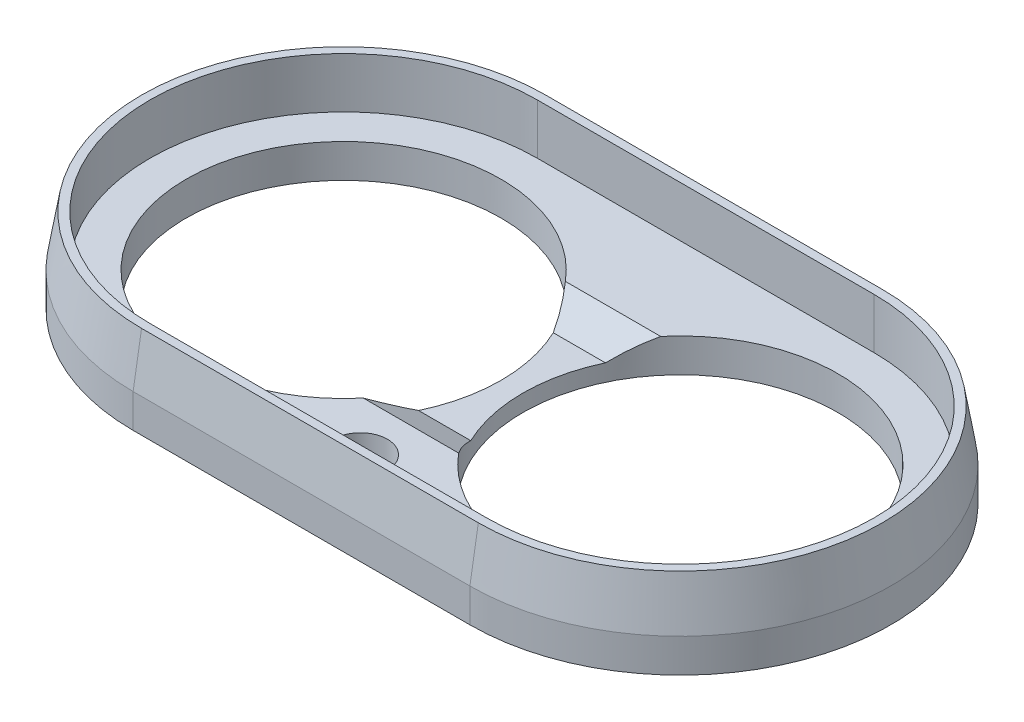
SolidWorks part; units mm, degrees
ref_plane "Front Plane" through (0, 0, 0) normal (0, 0, 1) x (1, 0, 0)
ref_plane "Top Plane" through (0, 0, 0) normal (0, 1, 0) x (1, 0, 0)
ref_plane "Right Plane" through (0, 0, 0) normal (1, 0, 0) x (0, 0, -1)
sketch "Sketch1" plane through (0, 0, 0) normal (0, 1, 0) x (1, 0, 0)
  line L0 (-10, 0) -> (10, 0)
  line L1 (10, 0) -> (22.5, 0)
  line L2 (10, 12.5) -> (-10, 12.5)
  line L3 (0, 12.5) -> (0, -12.5)
  line L4 (0, 19.9863) -> (0, -22.3991) construction
  line L5 (33.4627, 0) -> (-36.5916, 0) construction
  line L6 (-10, 0) -> (-22.5, 0)
  line L7 (10, -12.5) -> (-10, -12.5)
  arc A0 (10, -12.5) -> (10, 12.5) centre (10, 0) ccw
  arc A1 (-10, -12.5) -> (-10, 12.5) centre (-10, 0) cw
  point P16 (0, 0)
  dimension "D1" = 10
extrude "Boss-Extrude1" add sketch "Sketch1" along normal blind 2 contours A1 L6 L0 L3 L2 | A1 L7 L3 L0 L6 | L7 A0 L1 L0 L3 | L1 A0 L2 L3 L0 region at (-10.1051, 0, -5.7819) region at (-10.1051, 0, 5.7819) region at (10.1051, 0, -5.7819) region at (10.1051, 0, 5.7819)
sketch "Sketch2" plane through (0, 2, 0) normal (0, 1, 0) x (1, 0, 0)
  line L0 (0, 15.683) -> (0, -16.5594) construction
  circle A1 centre (10, 0) radius 9.35
  circle A2 centre (-10, 0) radius 9.35
  dimension "D1" = 18.7
  dimension "D2" = 10
extrude "Cut-Extrude1" cut sketch "Sketch2" against normal through all
sketch "Sketch3" plane through (0, 2, 0) normal (0, 1, 0) x (1, 0, 0)
  line L2 (10, 11.5) -> (-10, 11.5)
  line L3 (-10, -11.5) -> (10, -11.5)
  line L4 (-10, -12.5) -> (10, -12.5)
  line L5 (10, 12.5) -> (-10, 12.5)
  line L6 (-10, -12.5) -> (10, -12.5)
  line L7 (10, 12.5) -> (-10, 12.5)
  arc A2 (-10, 11.5) -> (-10, -11.5) centre (-10, 0) ccw
  arc A3 (10, -11.5) -> (10, 11.5) centre (10, 0) ccw
  arc A4 (10, -12.5) -> (10, 12.5) centre (10, 0) ccw
  arc A5 (-10, 12.5) -> (-10, -12.5) centre (-10, 0) ccw
  arc A6 (10, -12.5) -> (10, 12.5) centre (10, 0) ccw
  arc A7 (-10, 12.5) -> (-10, -12.5) centre (-10, 0) ccw
  dimension "D1" = 0
  dimension "D2" = 1
extrude "Boss-Extrude2" add sketch "Sketch3" along normal blind 3
chamfer "Chamfer1" distance 3 distance2 0.5 4 edges at (0, 5, -12.5) (22.5, 5, 0) (0, 5, 12.5) (-22.5, 5, 0) first distance on face at (0, 2.5, -12.5) first distance on face at (16.25, 2.5, 0) first distance on face at (0, 2.5, 12.5) first distance on face at (-16.25, 2.5, 0)
sketch "Sketch4" plane through (0, 2, 0) normal (0, 1, 0) x (1, 0, 0)
  line L1 (-7.5, -6) -> (7.5, -6)
  line L2 (-7.5, -6) -> (-7.5, 6)
  line L3 (-7.5, 6) -> (7.5, 6)
  line L4 (7.5, -6) -> (7.5, 6)
  line L5 (-7.5, -6) -> (7.5, 6) construction
  line L6 (-7.5, 6) -> (7.5, -6) construction
  point P0 (0, 0)
  dimension "D1" = 15
  dimension "D2" = 12
extrude "Cut-Extrude2" cut sketch "Sketch4" against normal blind 1
chamfer "Chamfer2" distance 1 distance2 2 2 edges at (0, 1, 6) (0, 1, -6) first distance on face at (0, 1.5, 6) first distance on face at (0, 1.5, -6)
sketch "Sketch5" plane through (0, 0, 0) normal (0, -1, 0) x (1, 0, 0)
  line L0 (10, 12.5) -> (-10, 12.5) construction
  circle A0 centre (0, 9) radius 1.6
  circle A1 centre (-4.45, 9.5) radius 0.75
  circle A2 centre (4.45, 9.5) radius 0.75
  dimension "D6" = 1.5
  dimension "D7" = 1.5
  dimension "D8" = 3.2
  dimension "D1" = 3.5
  dimension "D2" = 3
  dimension "D3" = 3
  dimension "D4" = 4.45
  dimension "D5" = 4.45
extrude "Cut-Extrude3" cut sketch "Sketch5" against normal through all
